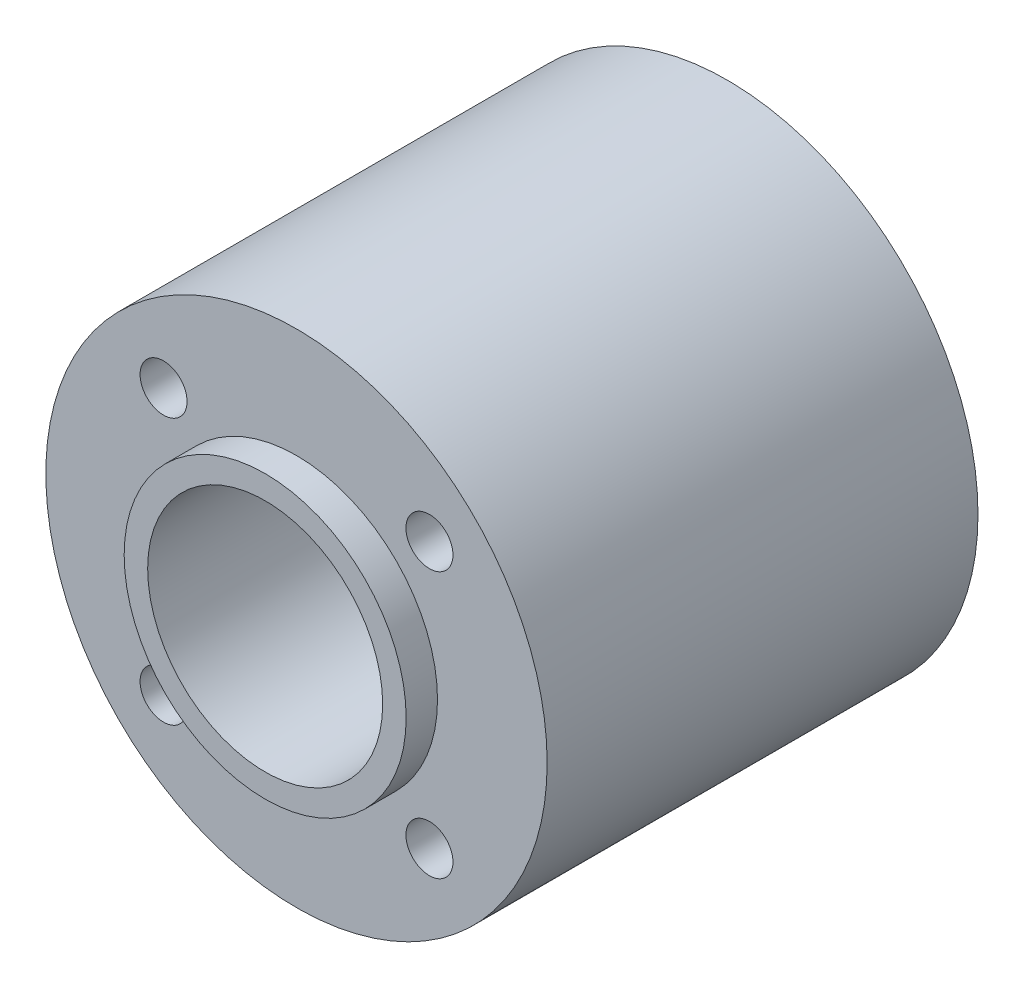
SolidWorks part; units mm, degrees
ref_plane "Front Plane" through (0, 0, 0) normal (0, 0, 1) x (1, 0, 0)
ref_plane "Top Plane" through (0, 0, 0) normal (0, 1, 0) x (1, 0, 0)
ref_plane "Right Plane" through (0, 0, 0) normal (1, 0, 0) x (0, 0, -1)
sketch "Sketch1" plane through (0, 0, 0) normal (0, 0, 1) x (1, 0, 0)
  circle A0 centre (0, 0) radius 16
  circle A1 centre (0, 0) radius 7.5
  circle A2 centre (0, 0) radius 9
  dimension "D1" = 32
  dimension "D2" = 18
  dimension "D3" = 15
extrude "Boss-Extrude1" add sketch "Sketch1" against normal blind 27.5 contours A0 A2 | A2 A1 region at (-15.5475, 0, 0) region at (-8.7454, 0, 0)
extrude "Boss-Extrude2" add sketch "Sketch1<3>" along normal blind 2 contours A2 A1 region at (-8.7454, 0, 0)
sketch "Sketch1<3>" plane through (0, 0, 0) normal (0, 0, 1) x (1, 0, 0) same geometry as "Sketch1"
extrude "Boss-Extrude3" add sketch "Sketch1<4>" against normal blind 2 from surface contours A2 A1 region at (-8.7454, 0, 0) starting at face at (16, 0, -27.5)
sketch "Sketch1<4>" plane through (0, 0, 0) normal (0, 0, 1) x (1, 0, 0) same geometry as "Sketch1"
sketch "Sketch2" plane through (0, 0, 0) normal (0, 0, 1) x (1, 0, 0)
  line L0 (0, 12) -> (0, 0) construction
  line L1 (0, 0) -> (-8.4853, 8.4853) construction
  circle A0 centre (0, 0) radius 12 construction
  circle A1 centre (-8.4853, 8.4853) radius 1.5
  circle A2 centre (8.4853, 8.4853) radius 1.5
  circle A3 centre (8.4853, -8.4853) radius 1.5
  circle A4 centre (-8.4853, -8.4853) radius 1.5
  circle A5 centre (0, 0) radius 16 construction
  point P15 (0, 0)
  dimension "D1" = 45
  dimension "D2" = 24
  dimension "D3" = 3
  dimension "D4" = 4
extrude "Cut-Extrude1" cut sketch "Sketch2" against normal through all
